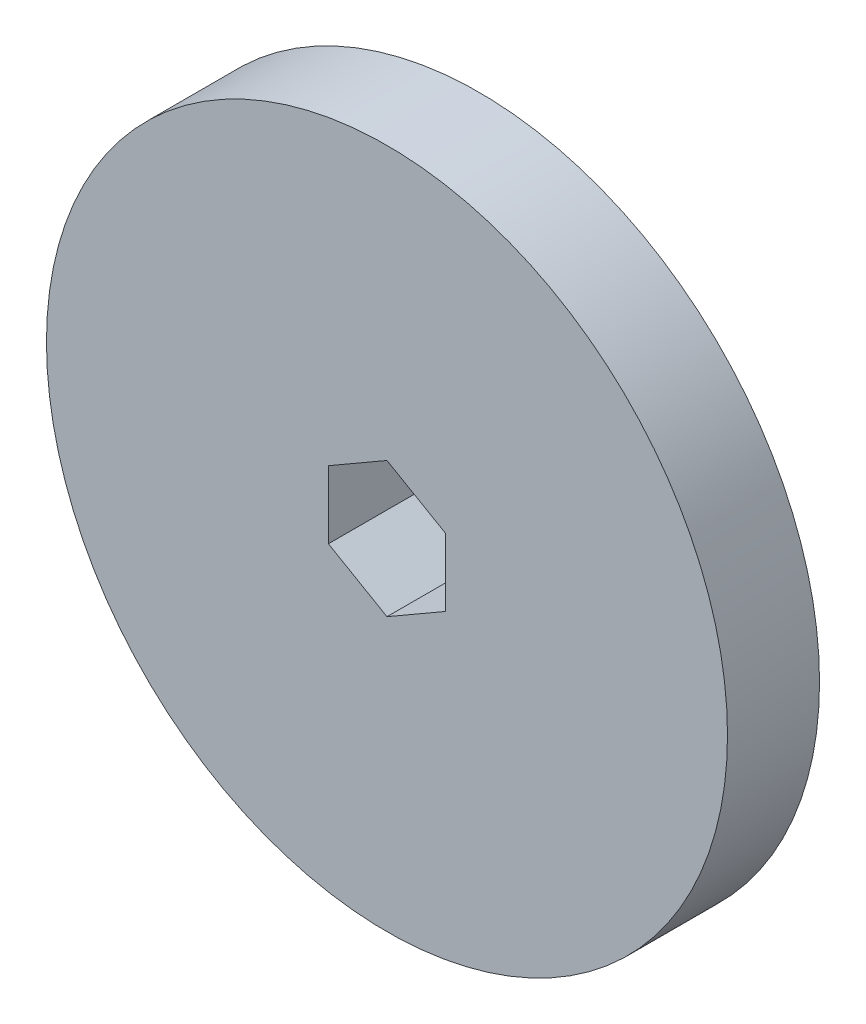
SolidWorks part; units mm, degrees
ref_plane "Front Plane" through (0, 0, 0) normal (0, 0, 1) x (1, 0, 0)
ref_plane "Top Plane" through (0, 0, 0) normal (0, 1, 0) x (1, 0, 0)
ref_plane "Right Plane" through (0, 0, 0) normal (1, 0, 0) x (0, 0, -1)
sketch "Sketch1" plane through (0, 0, 0) normal (0, 0, 1) x (1, 0, 0)
  circle A0 centre (0, 0) radius 37
  dimension "D1" = 74
extrude "Boss-Extrude2" add sketch "Sketch1" along normal blind 10
sketch "Sketch2" plane through (0, 0, 10) normal (0, 0, 1) x (1, 0, 0)
  line L1 (0, 7.3497) -> (-6.365, 3.6748)
  line L2 (-6.365, 3.6748) -> (-6.365, -3.6748)
  line L3 (-6.365, -3.6748) -> (0, -7.3497)
  line L4 (0, -7.3497) -> (6.365, -3.6748)
  line L5 (6.365, -3.6748) -> (6.365, 3.6748)
  line L6 (6.365, 3.6748) -> (0, 7.3497)
  circle A0 centre (0, 0) radius 6.365 construction
extrude "Cut-Extrude1" cut sketch "Sketch2" against normal blind 10
